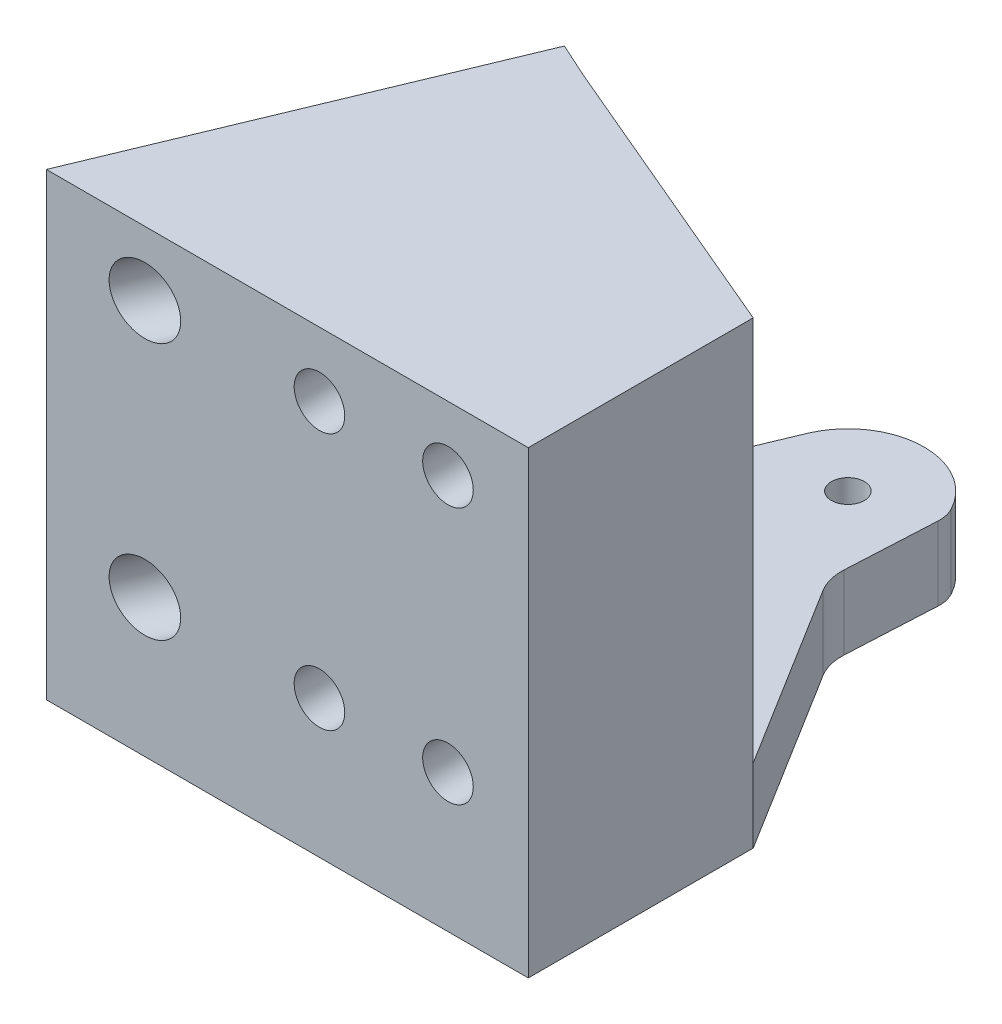
SolidWorks part; units mm, degrees
ref_plane "Front Plane" through (0, 0, 0) normal (0, 0, 1) x (1, 0, 0)
ref_plane "Top Plane" through (0, 0, 0) normal (0, 1, 0) x (1, 0, 0)
ref_plane "Right Plane" through (0, 0, 0) normal (1, 0, 0) x (0, 0, -1)
sketch "Sketch2" plane through (0, 0, 0) normal (0, 1, 0) x (1, 0, 0)
  line L0 (0, 0) -> (0, -15.6292)
  line L1 (0, -15.6292) -> (36.8202, -15.6292) construction
  line L2 (36.8202, -15.6292) -> (0, 0)
  line L5 (0, -15.6292) -> (0, -43.6292)
  line L6 (0, -43.6292) -> (36.8202, -43.6292)
  line L7 (36.8202, -15.6292) -> (36.8202, -43.6292)
  line L8 (18.4101, -43.6292) -> (18.4101, -15.6292) construction
  line L9 (0, -29.6292) -> (36.8202, -29.6292) construction
  point P282 (18.4101, -29.6292)
  dimension "D1" = 40
  dimension "D2" = 23
  dimension "D3" = 28
extrude "Boss-Extrude1" add sketch "Sketch2" along normal blind 48
sketch "Sketch4" plane through (0, 0, 43.6292) normal (0, 0, 1) x (1, 0, 0)
  line L0 (0, 48) -> (36.8202, 48) construction
  line L1 (10.8202, 40) -> (26.8202, 40) construction
  line L2 (10.8202, 40) -> (10.8202, 8) construction
  line L3 (10.8202, 8) -> (26.8202, 8) construction
  line L4 (26.8202, 40) -> (26.8202, 8) construction
  line L5 (18.8202, 8) -> (18.8202, 40) construction
  line L6 (10.8202, 24) -> (26.8202, 24) construction
  line L7 (36.8202, 48) -> (36.8202, 0) construction
  circle A0 centre (10.8202, 40) radius 3.15
  circle A1 centre (26.8202, 40) radius 3.15
  circle A2 centre (10.8202, 8) radius 3.15
  circle A3 centre (26.8202, 8) radius 3.15
  circle A4 centre (10.8202, 40) radius 2
  circle A5 centre (26.8202, 40) radius 2
  circle A6 centre (10.8202, 8) radius 2
  circle A7 centre (26.8202, 8) radius 2
  point P197 (18.8202, 24)
  dimension "D1" = 6.3
  dimension "D2" = 6.3
  dimension "D3" = 6.3
  dimension "D4" = 6.3
  dimension "D9" = 4
  dimension "D10" = 4
  dimension "D11" = 4
  dimension "D12" = 4
  dimension "D5" = 16
  dimension "D6" = 32
  dimension "D7" = 8
  dimension "D8" = 10
extrude "Cut-Extrude2" cut sketch "Sketch4" against normal blind 4.7 contours A4 | A0 A4 | A1 A5 | A5 | A7 | A3 A7 | A6 | A2 A6 region at (7.7593, 40, 43.6292) region at (23.7593, 40, 43.6292) region at (7.7593, 8, 43.6292) region at (23.7593, 8, 43.6292) region at (10.8202, 40, 43.6292) region at (26.8202, 40, 43.6292) region at (10.8202, 8, 43.6292) region at (26.8202, 8, 43.6292)
sketch "Sketch6" plane through (0, 0, 0) normal (0, -1, 0) x (1, 0, 0)
  line L0 (36.8202, 15.6292) -> (22.2793, -22.9412)
  line L1 (0, 0) -> (4.0568, -21.3624)
  line L2 (4.0568, -21.3624) -> (0, 0)
  line L3 (36.8202, 43.6292) -> (0, 43.6292)
  line L4 (0, 0) -> (36.8202, 15.6292)
  line L5 (36.8202, 15.6292) -> (36.8202, 43.6292)
  line L6 (36.8202, 43.6292) -> (0, 43.6292)
  line L7 (0, 43.6292) -> (0, 0)
  line L9 (36.8202, 15.6292) -> (36.8202, 43.6292)
  line L10 (36.8202, 43.6292) -> (0, 43.6292)
  line L12 (22.2793, -22.9412) -> (21.5556, -8.9412)
  line L13 (21.5556, -8.9412) -> (36.8202, 15.6292)
  line L14 (0, 0) -> (-23.1798, 43.6292)
  line L15 (36.8202, 43.6292) -> (-23.1798, 43.6292)
  line L16 (-23.1798, 43.6292) -> (4.6178, -23.2368)
  line L17 (0, 0) -> (-4.2396, -1.9306)
  circle A0 centre (13.39, -19.59) radius 2.05
  arc A1 (4.0568, -21.3624) -> (22.2793, -22.9412) centre (13.39, -19.59) ccw
  line M5 (0, 0) -> (36.8202, 15.6292)
  line M6 (36.8202, 15.6292) -> (36.8202, 43.6292)
  line M7 (36.8202, 43.6292) -> (0, 43.6292)
  line M8 (0, 43.6292) -> (0, 0)
  dimension "D4" = 19
  dimension "4.1" = 4.1
  dimension "D2" = 13.39
  dimension "D3" = 19.59
  dimension "D5" = 14
  dimension "D6" = 60
  dimension "D1" = 0
extrude "Boss-Extrude3" add sketch "Sketch6" along normal blind 9.18 contours L1 A1 L12 L13 A0 M5 | L3 L2 M8 | M8 M5 M6 M7 | A1 L1 L14 | L17 L14 L16 region at (15.0842, 0, -7.6218) region at (17.0711, 0, 25.4377) region at (-7.7266, 0, 29.0862) region at (-9.1398, 0, 13.8996) region at (0.003, 0, -8.0956)
extrude "Cut-Extrude3" cut sketch "Sketch4<3>" against normal blind 8 contours A4 | A5 | A7 | A6 region at (10.8202, 40, 43.6292) region at (26.8202, 40, 43.6292) region at (10.8202, 8, 43.6292) region at (26.8202, 8, 43.6292)
sketch "Sketch4<3>" plane through (0, 0, 43.6292) normal (0, 0, 1) x (1, 0, 0) same geometry as "Sketch4"
fillet "Fillet3" radius 4 1 edges at (22.2793, -4.59, -22.9412)
fillet "Fillet4" radius 6 1 edges at (21.5556, -4.59, -8.9412)
extrude "Boss-Extrude4" add sketch "Sketch6<3>" against normal up to surface (48 mm away) contours L15 L14 M8 | L17 L14 L16 region at (-7.7266, 0, 29.0862) region at (-9.1398, 0, 13.8996) up to face at (18.4101, 48, 25.7219)
sketch "Sketch6<3>" plane through (0, 0, 0) normal (0, -1, 0) x (1, 0, 0) same geometry as "Sketch6"
sketch "Sketch3" plane through (0, 0, 0) normal (0.3907, 0, -0.9205) x (-0.9205, 0, -0.3907)
  line L0 (-7, 40) -> (-7, 8) construction
  line L1 (0, 48) -> (0, 0) construction
  line L2 (-40, 48) -> (0, 48) construction
  circle A0 centre (-7, 40) radius 4.1
  circle A1 centre (-7, 8) radius 4.1
  circle A2 centre (-7, 40) radius 2.05
  circle A3 centre (-7, 8) radius 2.05
  dimension "D2" = 8.2
  dimension "D3" = 4.1
  dimension "D5" = 4.1
  dimension "D1" = 32
  dimension "D4" = 7
  dimension "D6" = 8
extrude "Cut-Extrude6" cut sketch "Sketch3" against normal blind 66 from offset 5 contours A2 | A2 A0 | A3 | A1 A3 region at (10.1109, 40, 4.2918) region at (10.1109, 8, 4.2918) region at (6.4435, 40, 2.7351) region at (6.4435, 8, 2.7351) offset against normal yes
extrude "Cut-Extrude7" cut sketch "Sketch3<3>" against normal blind 7 contours A2 | A3 region at (6.4435, 40, 2.7351) region at (6.4435, 8, 2.7351)
sketch "Sketch3<3>" plane through (0, 0, 0) normal (0.3907, 0, -0.9205) x (-0.9205, 0, -0.3907) same geometry as "Sketch3"
